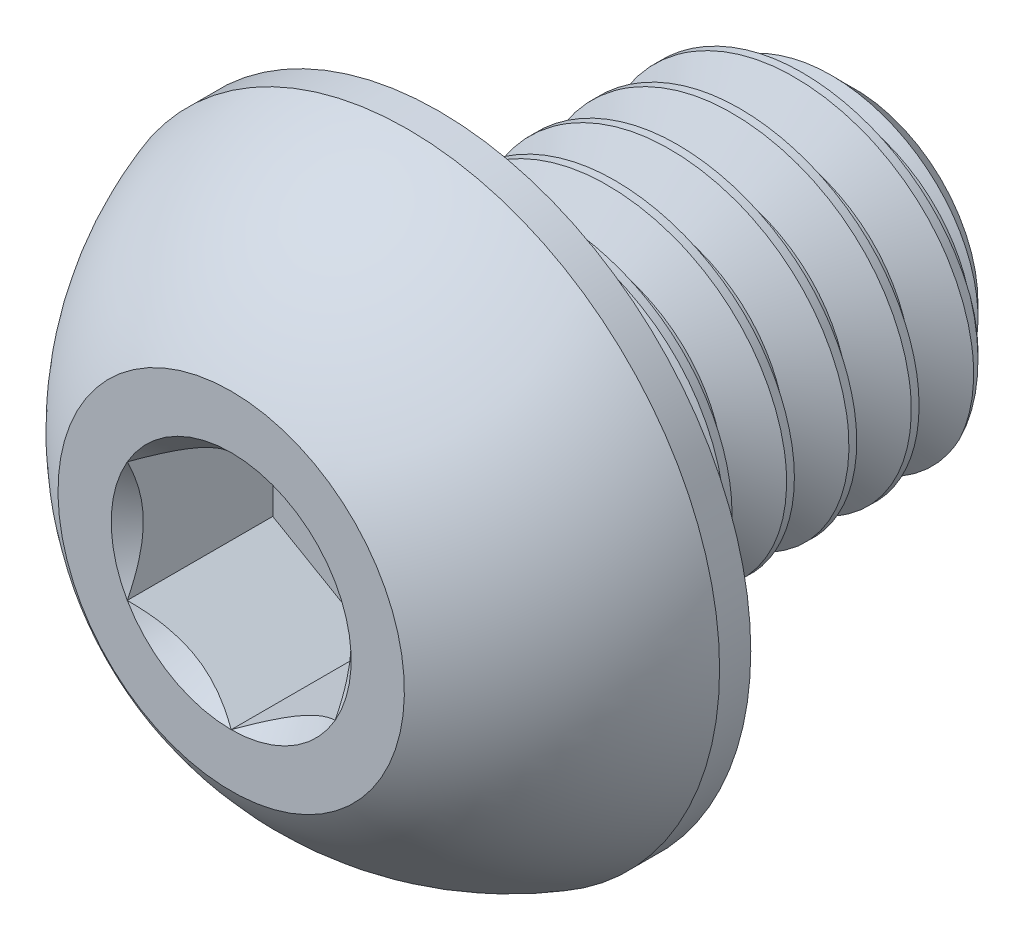
SolidWorks part; units mm, degrees
ref_plane "Front Plane" through (0, 0, 0) normal (0, 0, 1) x (1, 0, 0)
ref_plane "Top Plane" through (0, 0, 0) normal (0, 1, 0) x (1, 0, 0)
ref_plane "Right Plane" through (0, 0, 0) normal (1, 0, 0) x (0, 0, -1)
sketch "Sketch1" plane through (0, 0, 0) normal (1, 0, 0) x (0, 0, -1)
  line L0 (-2.25, 0) -> (2.25, 0) construction
  line L1 (-0.75, 2.25) -> (-0.75, -2.25) construction
  line L2 (2.25, 1.25) -> (2.25, -1.25) construction
  line L3 (2.2219, 1.2987) -> (2.4469, 0.909) construction
  line L4 (2.4469, 0.909) -> (2.6719, 1.2987) construction
  line L5 (2.6719, 1.2987) -> (2.2219, 1.2987) construction
  line L6 (2.25, 1.25) -> (2.6438, 1.25) construction
  line L7 (2.4469, 1.2987) -> (2.4469, 1.25) construction
  line L8 (2.4469, 1.25) -> (2.4469, 0.9577) construction
  line L9 (2.4469, 0.9577) -> (2.4469, 0.909) construction
  line L10 (2.4188, 0.9577) -> (2.475, 0.9577)
  line L11 (2.2359, 1.2744) -> (2.6578, 1.2744)
  line L12 (2.475, 0.9577) -> (2.6578, 1.2744)
  line L13 (2.4188, 0.9577) -> (2.2359, 1.2744)
  line L14 (-2.25, 0.75) -> (-2.25, -0.75) construction
  line L15 (2.25, 1.25) -> (-0.75, 1.25) construction
  point P3 (-0.75, 0)
  point P6 (-1.2, 0)
  point P21 (2.4469, 1.2744)
  point P24 (-0.975, 2.25)
  point P25 (1.125, -1.25)
  point P26 (-2.25, 1.25)
  dimension "Head Height" = 1.5
  dimension "Length" = 3
  dimension "Head Dia" = 4.5
  dimension "Thread Dia" = 2.5
  dimension "Pitch" = 0.45
  dimension "D2" = 0.0563
  dimension "Drive Size" = 1.5
  dimension "D1" = 1.05
  dimension "D3" = 0.225
  dimension "D4" = 1.125
sketch "Sketch2" plane through (0, 0, 0) normal (1, 0, 0) x (0, 0, -1)
  line L0 (-2.25, 0) -> (2.25, 0)
  line L1 (2.25, 0) -> (2.25, 0.89)
  line L2 (2.25, 1.25) -> (2.25, -1.25) construction
  line L3 (2.25, 0.89) -> (1.89, 1.25)
  line L4 (1.89, 1.25) -> (-0.75, 1.25)
  line L5 (-0.75, 2.25) -> (-0.75, -2.25) construction
  line L6 (-0.75, 1.25) -> (-0.75, 2.25)
  line L7 (-0.75, 2.25) -> (-0.975, 2.25)
  line L8 (2.25, 1.25) -> (2.6438, 1.25) construction
  line L9 (-2.25, 0) -> (-2.25, 1.25)
  arc A0 (-2.25, 1.25) -> (-0.975, 2.25) centre (-0.24, 0) cw
  dimension "D1" = 0.36
  dimension "D2" = 45
revolve "Revolve1" add sketch "Sketch2" angle 360 about L0
sketch "Sketch3" plane through (0, 0, 2.25) normal (0, 0, 1) x (1, 0, 0)
  line L1 (0, 0.866) -> (-0.75, 0.433)
  line L2 (-0.75, 0.433) -> (-0.75, -0.433)
  line L3 (-0.75, -0.433) -> (0, -0.866)
  line L4 (0, -0.866) -> (0.75, -0.433)
  line L5 (0.75, -0.433) -> (0.75, 0.433)
  line L6 (0.75, 0.433) -> (0, 0.866)
  circle A0 centre (0, 0) radius 0.75 construction
  dimension "D1" = 1.5
extrude "Cut-Extrude1" cut sketch "Sketch3" against normal up to vertex (1.05 mm away) up to point (0, 0, 1.2)
sketch "Sketch4" plane through (0, 0, 2.25) normal (0, 0, 1) x (1, 0, 0)
  circle A0 centre (0, 0) radius 0.866
extrude "Cut-Extrude2" cut sketch "Sketch4" against normal blind 10 draft 45
split "Split1" bodies to split 106 resulting bodies 107 108 split by face at (0, -2.25, 0.75)
sketch "Sketch5" plane through (0, 0, -2.25) normal (0, 0, -1) x (-1, 0, 0)
  circle A0 centre (0, 0) radius 1.25 construction
  circle A1 centre (0, 0) radius 1.25
curve "Helix/Spiral1" pitch 0.45 height 3.45 radius 1.25 centre (0, 0, -2.25) axis (0, 0, 1) start towards (0, 1, 0)
sketch "Sketch6" plane through (0, 0, 0) normal (1, 0, 0) x (0, 0, -1)
  line L0 (2.4188, 0.9577) -> (2.475, 0.9577) construction
  line L1 (2.4188, 0.9577) -> (2.2359, 1.2744) construction
  line L2 (2.2359, 1.2744) -> (2.6578, 1.2744) construction
  line L3 (2.475, 0.9577) -> (2.6578, 1.2744) construction
  line L4 (2.4188, 0.9577) -> (2.475, 0.9577)
  line L5 (2.4188, 0.9577) -> (2.2359, 1.2744)
  line L6 (2.2359, 1.2744) -> (2.6578, 1.2744)
  line L7 (2.475, 0.9577) -> (2.6578, 1.2744)
sweep "Cut-Sweep1" cut profiles "Sketch6" path "Helix/Spiral1" align with end faces yes
sketch "Sketch7" plane through (0, 0, 0.75) normal (0, 0, -1) x (-1, 0, 0)
  circle A1 centre (0, 0) radius 1.25
  circle A2 centre (0, 0) radius 1.25
  dimension "D1" = 0
extrude "Boss-Extrude1" add sketch "Sketch7" along normal blind 10 draft 30
equation "\"D2@Sketch1\" = \"Pitch@Sketch1\" / 8"
equation "\"D1@Sketch1\"=\"Drive Size@Sketch1\"*.7"
equation "\"D3@Sketch1\"=\"Head Height@Sketch1\"*.15"
equation "\"D1@Sketch2\"=\"Pitch@Sketch1\"*.8"
equation "\"D1@Sketch3\"=\"Drive Size@Sketch1\""
equation "\"D4@Helix/Spiral1\"=\"Pitch@Sketch1\""
equation "\"D3@Helix/Spiral1\"=\"Length@Sketch1\"+\"Pitch@Sketch1\""
equation "\"D4@Sketch1\"=\"Pitch@Sketch1\"*2.5"
